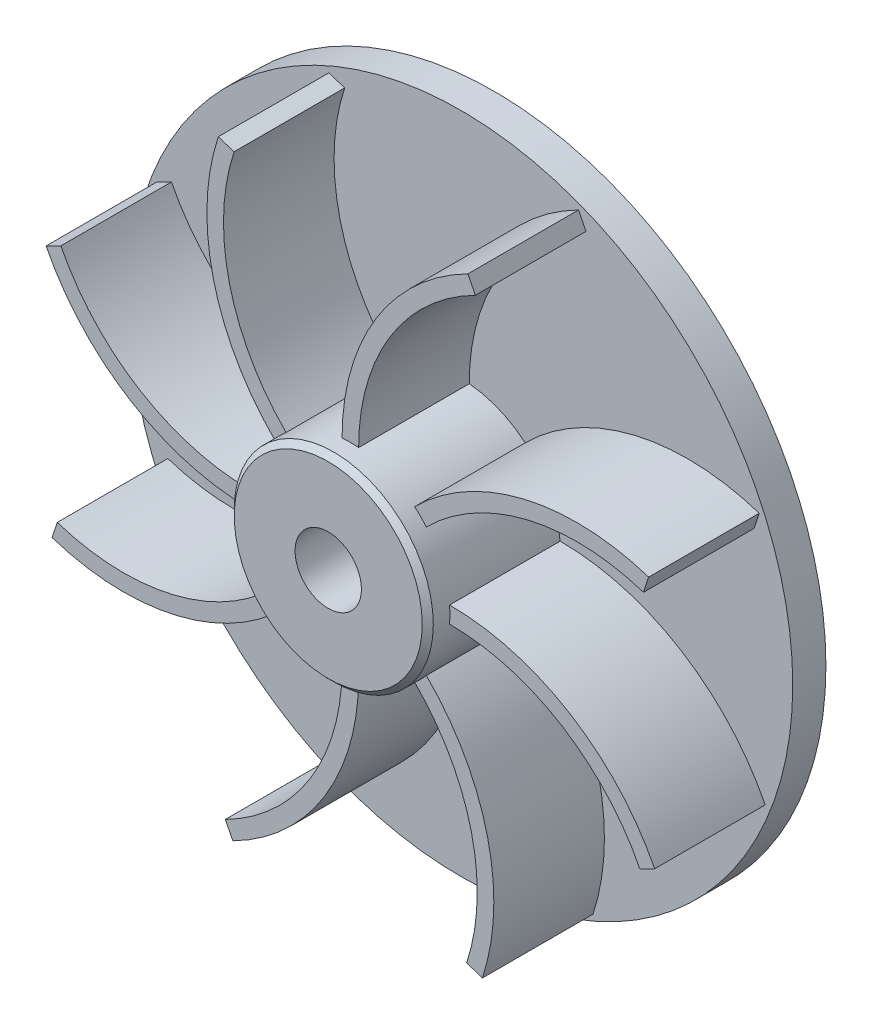
SolidWorks part; units mm, degrees
ref_plane "前视基准面" through (0, 0, 0) normal (0, 0, 1) x (1, 0, 0)
ref_plane "上视基准面" through (0, 0, 0) normal (0, 1, 0) x (1, 0, 0)
ref_plane "右视基准面" through (0, 0, 0) normal (1, 0, 0) x (0, 0, -1)
sketch "草图1" plane through (0, 0, 0) normal (0, 0, 1) x (1, 0, 0)
  circle A0 centre (0, 0) radius 60
extrude "凸台-拉伸1" add sketch "草图1" along normal blind 6
sketch "草图2" plane through (0, 0, 0) normal (0, 0, 1) x (1, 0, 0)
  circle A0 centre (0, 0) radius 18
extrude "凸台-拉伸2" add sketch "草图2" along normal blind 30
ref_plane "基准面1" through (0, 0, 6) normal (0, 0, 1) x (1, 0, 0)
sketch "草图3" plane through (0, 0, 6) normal (0, 0, 1) x (1, 0, 0)
  line L0 (10.7936, 0.8695) -> (11.3145, -2.0849)
  line L1 (52.3494, -22.6112) -> (55.026, -21.2563)
  arc A0 (55.026, -21.2563) -> (10.7936, 0.8695) centre (18, -40) ccw
  arc A1 (11.3145, -2.0849) -> (52.3494, -22.6112) centre (18, -40) cw
extrude "凸台-拉伸3" add sketch "草图3" along normal blind 20
ref_axis "基准轴1" through (0, 0, 31.5) along (0, 0, -1)
pattern_circular "阵列(圆周)1" count 8 over 360 about axis through (0, 0, 31.5) along (0, 0, -1) of "凸台-拉伸3"
ref_plane "基准面2" through (0, 0, 30) normal (0, 0, 1) x (1, 0, 0)
sketch "草图4" plane through (0, 0, 30) normal (0, 0, 1) x (1, 0, 0)
  circle A0 centre (0, 0) radius 6
extrude "切除-拉伸1" cut sketch "草图4" against normal through all
chamfer "倒角1" distance 1 angle 45 1 edges at (18, 0, 30)
